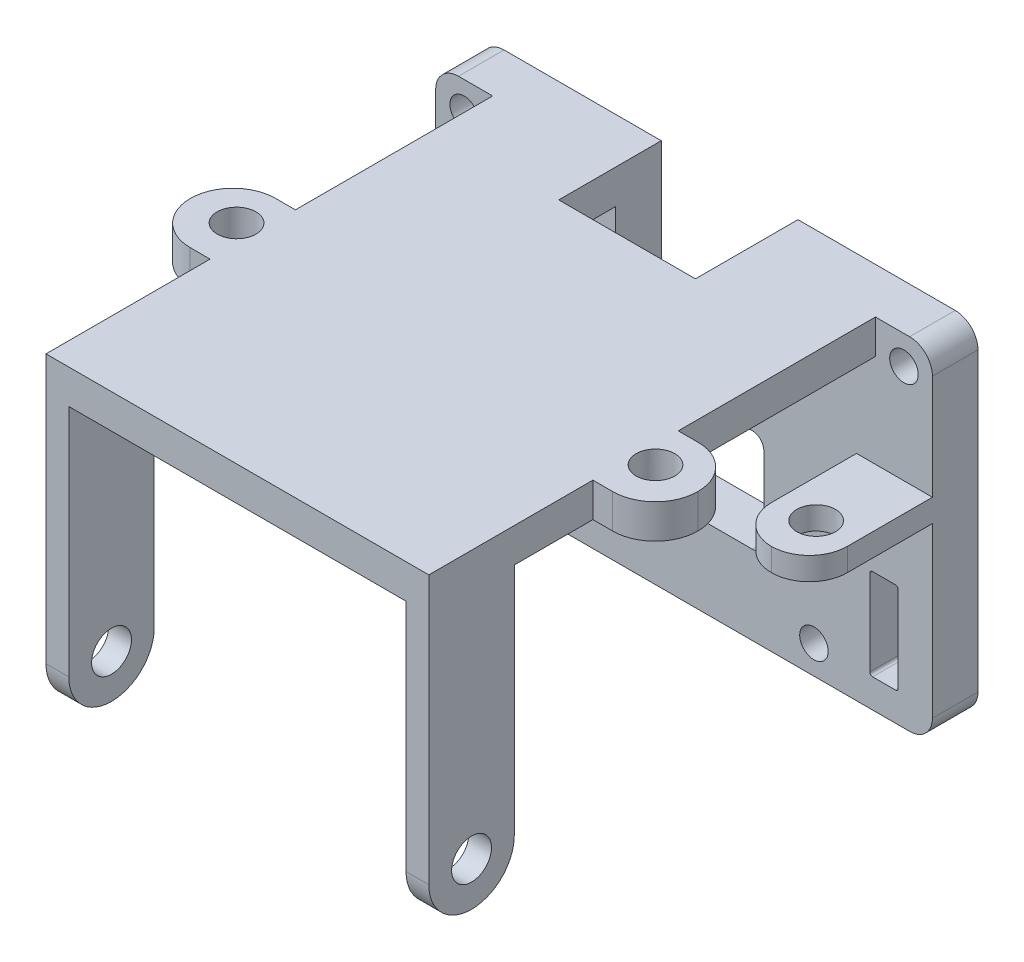
SolidWorks part; units mm, degrees
ref_plane "Front Plane" through (0, 0, 0) normal (0, 0, 1) x (1, 0, 0)
ref_plane "Top Plane" through (0, 0, 0) normal (0, 1, 0) x (1, 0, 0)
ref_plane "Right Plane" through (0, 0, 0) normal (1, 0, 0) x (0, 0, -1)
sketch "Sketch1" plane through (0, 0, 0) normal (0, 0, 1) x (1, 0, 0)
  line L1 (-16.8, -15) -> (16.8, -15)
  line L2 (-16.8, -15) -> (-16.8, 15)
  line L3 (-16.8, 15) -> (16.8, 15)
  line L4 (16.8, -15) -> (16.8, 15)
  line L5 (-16.8, -15) -> (16.8, 15) construction
  line L6 (-16.8, 15) -> (16.8, -15) construction
  point P0 (0, 0)
  dimension "D1" = 33.6
  dimension "D2" = 30
extrude "Boss-Extrude1" add sketch "Sketch1" along normal blind 4
sketch "Sketch3" plane through (0, 0, 4) normal (0, 0, 1) x (1, 0, 0)
  line L0 (16.8, -15) -> (16.8, 15) construction
  line L1 (-16.8, 15) -> (16.8, 15)
  line L2 (-16.8, 15) -> (-16.8, 12)
  line L3 (-16.8, 12) -> (16.8, 12)
  line L4 (16.8, 15) -> (16.8, 12)
  dimension "D1" = 3
extrude "Boss-Extrude2" add sketch "Sketch3" along normal blind 39.2
sketch "Sketch5" plane through (0, 0, 4) normal (0, 0, 1) x (1, 0, 0)
  line L1 (-7, -8.05) -> (7, -8.05)
  line L2 (-7, -8.05) -> (-7, 0.95)
  line L3 (-7, 0.95) -> (7, 0.95)
  line L4 (7, -8.05) -> (7, 0.95)
  line L5 (-7, -8.05) -> (7, 0.95) construction
  line L6 (-7, 0.95) -> (7, -8.05) construction
  point P0 (0, -3.55)
  dimension "D1" = 14
  dimension "D2" = 9
extrude "Cut-Extrude2" cut sketch "Sketch5" against normal blind 30
sketch "Sketch8" plane through (0, 0, 4) normal (0, 0, 1) x (1, 0, 0)
  line L1 (6, 12) -> (-6, 12)
  line L2 (6, 12) -> (6, 5)
  line L3 (6, 5) -> (-6, 5)
  line L4 (-6, 12) -> (-6, 5)
  line L5 (6, 12) -> (-6, 5) construction
  line L6 (-6, 12) -> (6, 5) construction
  point P6 (0, 8.5)
  dimension "D1" = 7
  dimension "D2" = 12
extrude "Cut-Extrude4" cut sketch "Sketch8" against normal through all
sketch "Sketch10" plane through (0, 12, 0) normal (0, -1, 0) x (1, 0, 0)
  line L0 (16.8, 43.2) -> (16.8, 4) construction
  line L1 (16.8, 43.2) -> (14.8, 43.2)
  line L2 (16.8, 43.2) -> (16.8, 35.7)
  line L3 (16.8, 35.7) -> (14.8, 35.7)
  line L4 (14.8, 43.2) -> (14.8, 35.7)
  line L5 (-16.8, 43.2) -> (16.8, 43.2) construction
  dimension "D1" = 2
  dimension "D3" = 7.5
extrude "Boss-Extrude3" add sketch "Sketch10" along normal blind 24.3
sketch "Sketch12" plane through (16.8, 0, 0) normal (1, 0, 0) x (0, 0, -1)
  line L0 (-4, -15) -> (-4, 12) construction
  line L1 (-4, 15) -> (0, 15)
  line L2 (-4, 15) -> (-4, -15)
  line L3 (-4, -15) -> (0, -15)
  line L4 (0, 15) -> (0, -15)
  line L5 (0, -15) -> (0, 15) construction
  dimension "D1" = 30
extrude "Boss-Extrude4" add sketch "Sketch12" along normal blind 5
sketch "Sketch13" plane through (0, 0, 4) normal (0, 0, 1) x (1, 0, 0)
  line L0 (18.8, -12.475) -> (16.3, -12.475)
  line L1 (18.8, -12.475) -> (18.8, -4.475)
  line L2 (16.3, -12.475) -> (16.3, -4.475)
  line L3 (18.8, -4.475) -> (16.3, -4.475)
  line L4 (18.8, -12.475) -> (16.3, -4.475) construction
  line L5 (16.3, -12.475) -> (18.8, -4.475) construction
  line L6 (-16.8, -15) -> (21.8, -15) construction
  line L7 (21.8, 15) -> (21.8, -15) construction
  dimension "D1" = 2.5
  dimension "D2" = 8
  dimension "D3" = 2.525
  dimension "D4" = 3
extrude "Cut-Extrude5" cut sketch "Sketch13" against normal through all
fillet "Fillet3" radius 0.25 4 edges at (16.3, -12.475, 2) (18.8, -12.475, 2) (18.8, -4.475, 2) (16.3, -4.475, 2)
fillet "Fillet4" radius 1 6 edges at (7, -8.05, 2) (-7, -8.05, 2) (-7, 0.95, 2) (7, 0.95, 2) (-6, 5, 2) (6, 5, 2)
sketch "Sketch15" plane through (16.8, 0, 0) normal (1, 0, 0) x (0, 0, -1)
  line L0 (-43.2, -12.3) -> (-43.2, 12) construction
  line L1 (-35.7, -12.3) -> (-43.2, -12.3) construction
  circle A1 centre (-39.45, -8.475) radius 1.75
  dimension "D1" = 3.825
  dimension "D2" = 3.75
extrude "Cut-Extrude6" cut sketch "Sketch15" against normal up to next
ref_plane "Plane1" through (0, 0, 0) normal (-1, 0, 0) x (0, 0, 1)
fillet "Fillet6" radius 3.75 2 edges at (15.8, -12.3, 35.7) (15.8, -12.3, 43.2)
sketch "Sketch23" plane through (0, 0, 4) normal (0, 0, 1) x (1, 0, 0)
  line L1 (21.8, 15) -> (21.8, -15) construction
  line L2 (21.8, 15) -> (16.8, 15) construction
  circle A0 centre (11.4, -12.5) radius 1.25
  circle A1 centre (19.3, 12.5) radius 1.25
  dimension "D3" = 2.5
  dimension "D4" = 2.5
  dimension "D5" = 2.5
extrude "Cut-Extrude8" cut sketch "Sketch23" against normal up to next
fillet "Fillet8" radius 2 2 edges at (21.8, 15, 2) (21.8, -15, 2)
sketch "Sketch24" plane through (0, 15, 0) normal (0, 1, 0) x (1, 0, 0)
  line L1 (-6, -9) -> (6, -9)
  line L2 (-6, -9) -> (-6, 9)
  line L3 (-6, 9) -> (6, 9)
  line L4 (6, -9) -> (6, 9)
  line L5 (-6, -9) -> (6, 9) construction
  line L6 (-6, 9) -> (6, -9) construction
  point P0 (0, 0)
  dimension "D1" = 12
  dimension "D2" = 18
extrude "Cut-Extrude9" cut sketch "Sketch24" against normal up to next
sketch "Esboço1" plane through (16.8, 0, 0) normal (1, 0, 0) x (0, 0, -1)
  line L0 (-43.2, 15) -> (-4, 15) construction
  line L1 (-28.8, 15) -> (-21.31, 15)
  line L2 (-28.8, 15) -> (-28.8, 12)
  line L3 (-28.8, 12) -> (-21.31, 12)
  line L4 (-21.31, 15) -> (-21.31, 12)
  line L5 (-35.7, 12) -> (-4, 12) construction
  line L6 (-4, 15) -> (-4, 12) construction
  dimension "D1" = 17.31
  dimension "D2" = 7.49
extrude "Ressalto-extrusão1" add sketch "Esboço1" along normal blind 5.475
fillet "Filete1" radius 3.7338 1 edges at (22.275, 13.5, 28.8)
fillet "Filete2" radius 3.7338 1 edges at (22.275, 13.5, 21.31)
sketch "Esboço2" plane through (0, 15, 0) normal (0, 1, 0) x (1, 0, 0)
  circle A0 centre (18.385, -24.89) radius 1.7
  dimension "D1" = 3.4
  dimension "D2" = 3.89
  dimension "D3" = 3.91
extrude "Corte-extrusão1" cut sketch "Esboço2" against normal blind 5
sketch "Esboço3" plane through (0, 0, 4) normal (0, 0, 1) x (1, 0, 0)
  line L0 (21.8, 13) -> (21.8, -13) construction
  line L1 (21.8, 3.8) -> (15.14, 3.8)
  line L2 (21.8, 3.8) -> (21.8, 1.8)
  line L3 (21.8, 1.8) -> (15.14, 1.8)
  line L4 (15.14, 3.8) -> (15.14, 1.8)
  dimension "D1" = 8.2
  dimension "D2" = 0
  dimension "D3" = 2
  dimension "D4" = 6.66
extrude "Ressalto-extrusão2" add sketch "Esboço3" along normal blind 10.8
sketch "Esboço5" plane through (0, 3.8, 0) normal (0, 1, 0) x (1, 0, 0)
  line L0 (15.14, -14.8) -> (21.8, -14.8) construction
  line L1 (21.8, -14.8) -> (21.8, -4) construction
  circle A0 centre (18.47, -10.875) radius 1.7
  dimension "D2" = 3.4
  dimension "D1" = 3.925
  dimension "D3" = 3.33
extrude "Corte-extrusão2" cut sketch "Esboço5" against normal up to next
fillet "Filete3" radius 3.33 1 edges at (21.8, 2.8, 14.8)
fillet "Filete4" radius 3.33 1 edges at (15.14, 2.8, 14.8)
mirror "Espelhar5" about plane through (0, 0, 0) normal (-1, 0, 0) of "Filete3", "Corte-extrusão2", "Filete4", "Filete2", "Ressalto-extrusão1", "Filete1", "Corte-extrusão1", "Ressalto-extrusão2", "Boss-Extrude4", "Fillet8", "Cut-Extrude8", "Fillet3", "Cut-Extrude5", "Fillet6", "Boss-Extrude3", "Cut-Extrude6"
